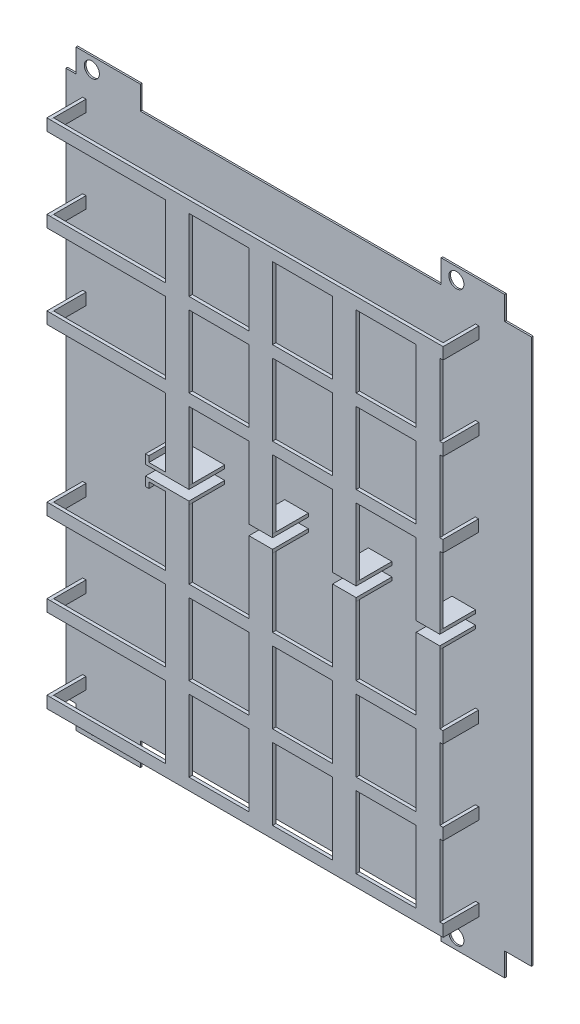
SolidWorks part; units mm, degrees
ref_plane "Płaszczyzna XY" through (0, 0, 0) normal (0, 0, 1) x (1, 0, 0)
ref_plane "Płaszczyzna XZ" through (0, 0, 0) normal (0, 1, 0) x (1, 0, 0)
ref_plane "Płaszczyzna YZ" through (0, 0, 0) normal (1, 0, 0) x (0, 0, -1)
sketch "Sketch1" plane through (0, 0, 125) normal (0, 0, -1) x (-1, 0, 0)
  line L0 (125.6611, -151.3707) -> (-48.3389, -151.3641) construction
  line L1 (125.6611, -151.3707) -> (-48.3389, -151.3641) construction
  line L2 (-48.3361, -77.3641) -> (-48.3389, -151.3641) construction
  line L3 (-48.3361, -77.3641) -> (-48.3389, -151.3641) construction
  line L4 (125.6727, 154.6293) -> (125.6699, 80.6293) construction
  line L5 (-81.7124, 0.0031) -> (196.6708, -0.0076)
  line L6 (-81.7124, 0.0031) -> (-81.7062, 164.6371)
  line L7 (-81.7062, 164.6371) -> (-65.7062, 164.6365)
  line L8 (196.6708, -0.0076) -> (196.6708, 164.6265)
  line L9 (125.6727, 154.6293) -> (125.6699, 80.6293) construction
  line L10 (125.6727, 154.6293) -> (-48.3273, 154.6359) construction
  line L11 (125.6727, 154.6293) -> (-48.3273, 154.6359) construction
  line L13 (-78.7182, -151.363) -> (-78.7063, 161.637) construction
  line L14 (193.6708, 161.6293) -> (193.6708, 104.6269) construction
  line L15 (190.6708, 164.6268) -> (190.6708, 178.6268)
  line L16 (190.6708, 178.6268) -> (152.1708, 178.6282)
  line L17 (152.1708, 178.6282) -> (152.1708, 164.6282)
  line L18 (190.6708, 164.6268) -> (196.6708, 164.6265)
  line L19 (-65.7062, 164.6365) -> (-65.7056, 178.6365)
  line L20 (-65.7056, 178.6365) -> (-27.7056, 178.6351)
  line L21 (-27.7056, 178.6351) -> (-27.7062, 164.6351)
  line L22 (-27.7062, 164.6351) -> (152.1708, 164.6282)
  circle A0 centre (181.1831, 171.6285) radius 4.5
  circle A1 centre (-36.8169, 171.6354) radius 4.5
  point P28 (0, 0)
  dimension "D7" = 9
  dimension "D11" = 9
  dimension "D1" = 3
  dimension "D2" = 10
  dimension "D3" = 3
  dimension "D4" = 14
  dimension "D5" = 6
  dimension "D6" = 44.5
  dimension "D8" = 16
  dimension "D9" = 54
  dimension "D10" = 14
extrude "Boss-Extrude1" add sketch "Sketch1" along normal blind 1
sketch "Sketch3" plane through (0, 0, 125) normal (0, 0, 1) x (1, 0, 0)
  line L0 (-125.6671, 6.6293) -> (48.3329, 6.6359) construction
  line L1 (-115.816, 6.6296) -> (-101.7106, 6.6302)
  line L2 (-115.816, 6.6296) -> (-115.8161, 4.6296)
  line L3 (-115.8161, 4.6296) -> (-101.7107, 4.6302)
  line L4 (-101.7107, 4.6302) -> (-101.7106, 6.6302)
  dimension "D1" = 2
extrude "Boss-Extrude2" add sketch "Sketch3" along normal blind 21.4
sketch "Sketch4" plane through (-0.0003, 6.634, 0) normal (0, 1, 0) x (1, 0, 0)
  line L0 (-101.7103, -146.4) -> (-115.8158, -146.4) construction
  line L1 (-101.7103, -146.4) -> (-115.8158, -146.4)
  line L2 (-101.7103, -146.4) -> (-101.7103, -125) construction
  line L3 (-101.7103, -146.4) -> (-101.7103, -144.4)
  line L4 (-115.8158, -146.4) -> (-115.8158, -125) construction
  line L5 (-115.8158, -146.4) -> (-115.8158, -144.4)
  line L6 (-125.6668, -144.4) -> (48.3332, -144.4) construction
  line L7 (-115.8158, -144.4) -> (-101.7103, -144.4)
extrude "Boss-Extrude3" add sketch "Sketch4" along normal up to surface (148 mm away)
pattern_linear "LPattern2" count 1 spacing 50 along (0, -1, 0) count 4 spacing 50 along (1, 0, 0) of "Boss-Extrude2"
pattern_linear "LPattern3" count 4 spacing 50 along (1, 0, 0) of "Boss-Extrude3"
sketch "Sketch5" plane through (0, 0, 125) normal (0, 0, 1) x (1, 0, 0)
  line L0 (-184.6727, 154.627) -> (-184.6693, 64.627) construction
  line L1 (-184.6727, 154.627) -> (-184.6724, 147.627)
  line L2 (-184.6727, 154.627) -> (-186.6727, 154.627)
  line L3 (-186.6727, 154.627) -> (-186.6724, 147.627)
  line L4 (-186.6724, 147.627) -> (-184.6724, 147.627)
  dimension "D1" = 2
  dimension "D2" = 7
extrude "Boss-Extrude4" add sketch "Sketch5" along normal up to surface (21.4 mm away) up to face at (-108.7652, 55.2966, 146.4)
sketch "Sketch6" plane through (-184.6668, -0.007, 0) normal (1, 0, 0) x (0, 0, -1)
  line L0 (-146.4, 147.634) -> (-146.4, 154.634) construction
  line L1 (-146.4, 147.634) -> (-146.4, 154.634)
  line L2 (-146.4, 147.634) -> (-125, 147.634) construction
  line L3 (-146.4, 147.634) -> (-144.4, 147.634)
  line L4 (-146.4, 154.634) -> (-125, 154.634) construction
  line L5 (-146.4, 154.634) -> (-144.4, 154.634)
  line L8 (-144.4, 147.634) -> (-144.4, 154.634)
  dimension "D1" = 2
sketch "Sketch7" plane through (0, 0, 125) normal (0, 0, 1) x (1, 0, 0)
  line L0 (-115.8216, 154.6296) -> (-101.7162, 154.6302) construction
  line L1 (48.2838, 154.6359) -> (50.2952, 154.636)
  line L2 (48.2838, 154.6359) -> (48.2841, 147.6359)
  line L3 (48.2841, 147.6359) -> (50.2841, 147.636)
  line L4 (50.2952, 154.636) -> (50.2841, 147.636)
  line L5 (-115.8216, 154.6296) -> (-101.7162, 154.6302) construction
  line L7 (48.2838, 154.6359) -> (48.2894, 6.6359) construction
  line L8 (48.2838, 154.6359) -> (48.2894, 6.6359) construction
  dimension "D1" = 2
  dimension "D2" = 7
extrude "Boss-Extrude6" add sketch "Sketch7" along normal up to surface (21.4 mm away) up to face at (-108.7652, 55.2966, 146.4)
extrude "Boss-Extrude7" add sketch "Sketch6" along normal up to surface (218.8511 mm away) up to face at (34.1812, 80.6353, 145.4)
pattern_linear "LPattern4" count 3 spacing 50 along (0, -1, 0) of "Boss-Extrude4"
pattern_linear "LPattern5" count 3 spacing 50 along (0, -1, 0) of "Boss-Extrude7"
pattern_linear "LPattern6" count 3 spacing 50 along (-0.0016, -1, 0) of "Boss-Extrude6"
sketch "Sketch9" plane through (0, 0, 125) normal (0, 0, 1) x (1, 0, 0)
  line L0 (-115.8176, 47.6296) -> (-115.816, 6.6296) construction
  line L1 (-115.816, 6.6296) -> (-115.8159, 4.6296)
  line L2 (-115.8159, 4.6296) -> (-127.6659, 4.6292)
  line L4 (-125.6659, 6.6293) -> (-115.816, 6.6296)
  line L5 (-115.8161, 4.6296) -> (-101.7107, 4.6302) construction
  line L6 (-115.8161, 4.6296) -> (-101.7107, 4.6302) construction
  line L7 (-101.7106, 6.6302) -> (-115.816, 6.6296) construction
  line L8 (-101.7106, 6.6302) -> (-115.816, 6.6296) construction
  line L9 (-127.6659, 4.6292) -> (-127.6659, 10.1292)
  line L10 (-127.6659, 10.1292) -> (-125.6659, 10.1292)
  line L11 (-125.6659, 10.1292) -> (-125.6659, 6.6293)
  dimension "D1" = 2
  dimension "D2" = 5.5
  dimension "D3" = 11.85
extrude "Boss-Extrude8" add sketch "Sketch9" along normal up to surface (21.4 mm away) up to face at (-60.1451, 62.0118, 146.4)
ref_plane "Plane1" through (-0.0001, 1.634, 0) normal (0, 1, 0) x (1, 0, 0)
mirror "Mirror6" about plane through (-0.0001, 1.634, 0) normal (0, 1, 0) of bodies 116
